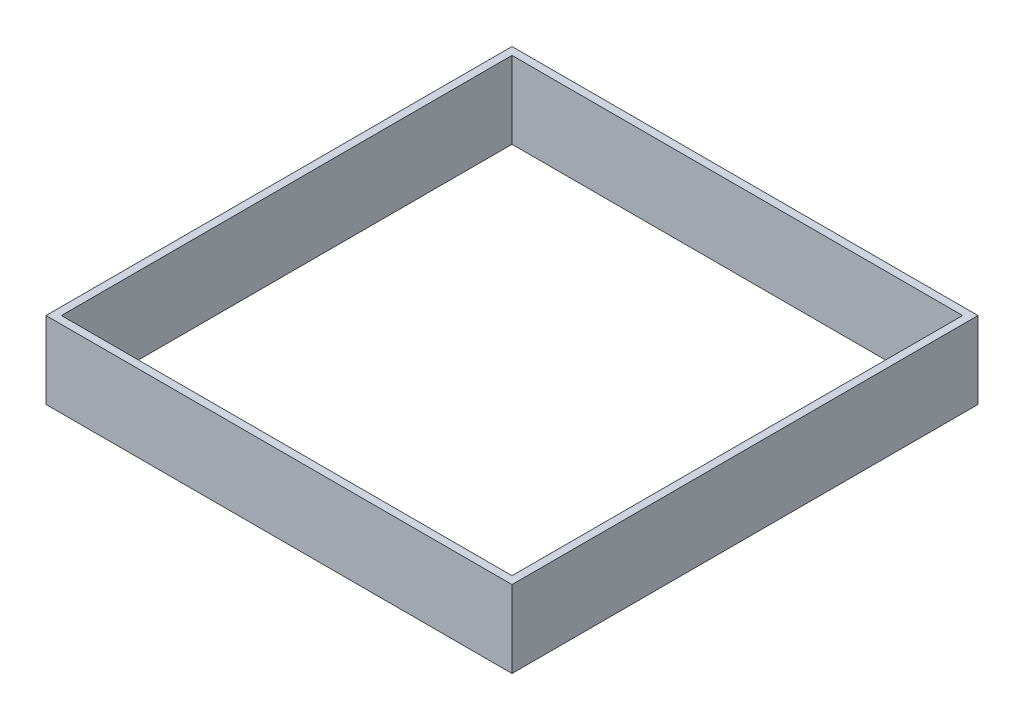
SolidWorks part; units mm, degrees
ref_plane "Front Plane" through (0, 0, 0) normal (0, 0, 1) x (1, 0, 0)
ref_plane "Top Plane" through (0, 0, 0) normal (0, 1, 0) x (1, 0, 0)
ref_plane "Right Plane" through (0, 0, 0) normal (1, 0, 0) x (0, 0, -1)
sketch "Sketch1" plane through (0, 0, 0) normal (0, 1, 0) x (1, 0, 0)
  line L1 (-60.5, -60.5) -> (60.5, -60.5)
  line L2 (-60.5, -60.5) -> (-60.5, 60.5)
  line L3 (-60.5, 60.5) -> (60.5, 60.5)
  line L4 (60.5, -60.5) -> (60.5, 60.5)
  line L5 (-60.5, -60.5) -> (60.5, 60.5) construction
  line L6 (-60.5, 60.5) -> (60.5, -60.5) construction
  line L7 (-58.5, -58.5) -> (58.5, -58.5)
  line L8 (-58.5, -58.5) -> (-58.5, 58.5)
  line L9 (-58.5, 58.5) -> (58.5, 58.5)
  line L10 (58.5, -58.5) -> (58.5, 58.5)
  line L11 (-58.5, -58.5) -> (58.5, 58.5) construction
  line L12 (-58.5, 58.5) -> (58.5, -58.5) construction
  point P0 (0, 0)
  point P6 (0, 0)
  dimension "D1" = 2
  dimension "D2" = 2
  dimension "D3" = 117
  dimension "D4" = 117
extrude "Boss-Extrude1" add sketch "Sketch1" along normal blind 20
